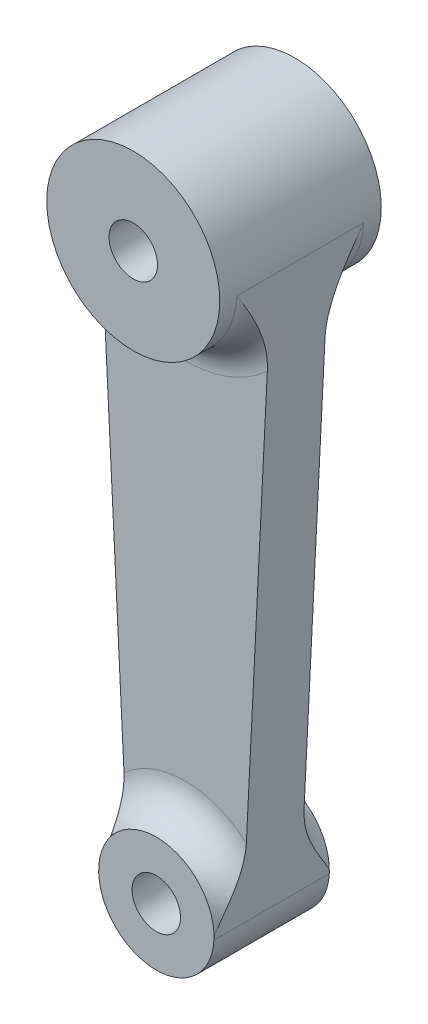
SolidWorks part; units mm, degrees
material "ABS"
ref_plane "Front Plane" through (0, 0, 0) normal (0, 0, 1) x (1, 0, 0)
ref_plane "Top Plane" through (0, 0, 0) normal (0, 1, 0) x (1, 0, 0)
ref_plane "Right Plane" through (0, 0, 0) normal (1, 0, 0) x (0, 0, -1)
sketch "Sketch1" plane through (0, 0, 0) normal (0, 0, 1) x (1, 0, 0)
  circle A0 centre (0, 0) radius 7.5
  dimension "D1" = 15
extrude "Boss-Extrude1" add sketch "Sketch1" along normal mid plane 14
sketch "Sketch2" plane through (0, 0, 7) normal (0, 0, 1) x (1, 0, 0)
  circle A0 centre (0, 0) radius 2.1
  circle A1 centre (0, 0) radius 7.5 construction
  dimension "D1" = 4.2
extrude "Cut-Extrude1" cut sketch "Sketch2" against normal through all both and the other way through all
sketch "Sketch3" plane through (0, 0, 0) normal (0, 0, 1) x (1, 0, 0)
  line L0 (-7.4906, -0.375) -> (-4.9937, -50.25)
  line L5 (7.4906, -0.375) -> (4.9937, -50.25)
  circle A1 centre (0, 0) radius 7.5 construction
  arc A2 (7.4906, -0.375) -> (-7.4906, -0.375) centre (0, 0) cw
  arc A3 (-4.9937, -50.25) -> (4.9937, -50.25) centre (0, -50) cw
  circle A4 centre (0, -50) radius 5
  dimension "D2" = 10
  dimension "D1" = 50
extrude "Boss-Extrude2" add sketch "Sketch3" along normal mid plane 5 contours L0 A3 L5 A2 region at (0, -24.9727, 0)
extrude "Boss-Extrude3" add sketch "Sketch3<3>" along normal mid plane 10 contours A3 A4 region at (0, -50, 0)
sketch "Sketch3<3>" plane through (0, 0, 0) normal (0, 0, 1) x (1, 0, 0) same geometry as "Sketch3"
fillet "Fillet1" radius 3 4 edges at (0, -45, 2.5) (0, -45, -2.5) (0, -7.5, -2.5) (0, -7.5, 2.5)
sketch "Sketch4" plane through (0, 0, 5) normal (0, 0, 1) x (1, 0, 0)
  circle A0 centre (0, -50) radius 2.1
  arc A1 (-4.9937, -50.25) -> (4.9937, -50.25) centre (0, -50) ccw construction
  dimension "D1" = 4.2
extrude "Cut-Extrude2" cut sketch "Sketch4" against normal up to next contours A0
